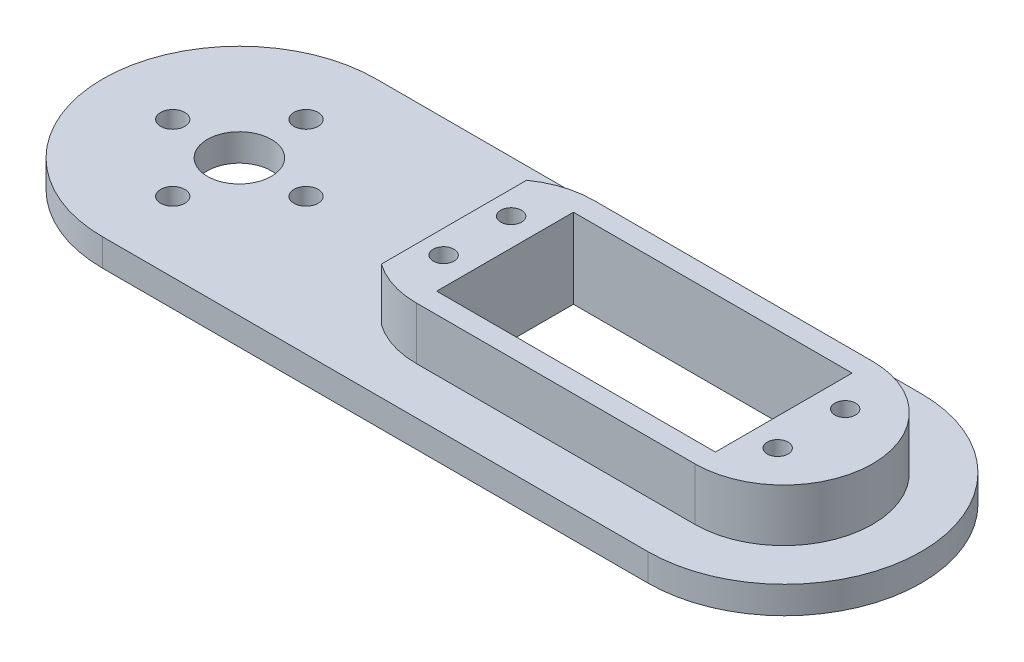
SolidWorks part; units mm, degrees
ref_plane "Front Plane" through (0, 0, 0) normal (0, 0, 1) x (1, 0, 0)
ref_plane "Top Plane" through (0, 0, 0) normal (0, 1, 0) x (1, 0, 0)
ref_plane "Right Plane" through (0, 0, 0) normal (1, 0, 0) x (0, 0, -1)
sketch "Sketch1" plane through (0, 0, 0) normal (0, 1, 0) x (1, 0, 0)
  line L0 (0, 15.5) -> (0, -15.5) construction
  line L1 (-15.5, 0) -> (15.5, 0) construction
  line L2 (-2.4674, 13.4022) -> (-4, 4) construction
  line L3 (4, -4) -> (-4, -4) construction
  line L4 (4, -4) -> (4, 4) construction
  line L5 (4, 4) -> (-4, 4) construction
  line L6 (-4, -4) -> (-4, 4) construction
  line L7 (4, -4) -> (-4, 4) construction
  line L8 (4, 4) -> (-4, -4) construction
  line L9 (-4, 4) -> (-2.4674, 13.4022)
  line L10 (4, 4) -> (2.4674, 13.4022)
  line L11 (4, -4) -> (2.4674, -13.4022)
  line L12 (-4, -4) -> (-2.4674, -13.4022)
  line L13 (-4, 4) -> (-12.5927, 2.4331) construction
  line L14 (-4, 4) -> (-12.4485, 2.4594)
  line L15 (-4, -4) -> (-12.4485, -2.4594)
  line L16 (4, -4) -> (12.4485, -2.4594)
  line L17 (4, 4) -> (12.4485, 2.4594)
  circle A0 centre (0, 0) radius 15.5 construction
  circle A1 centre (0, 0) radius 14.5 construction
  arc A2 (2.4674, 13.4022) -> (-2.4674, 13.4022) centre (0, 13) ccw
  arc A3 (2.4674, -13.4022) -> (-2.4674, -13.4022) centre (0, -13) cw
  arc A4 (-12.4485, 2.4594) -> (-12.4485, -2.4594) centre (-12, 0) ccw
  arc A5 (12.4485, 2.4594) -> (12.4485, -2.4594) centre (12, 0) cw
  circle A6 centre (0, 0) radius 12 construction
  circle A7 centre (0, 0) radius 9.5 construction
  circle A8 centre (0, 0) radius 7.5 construction
  circle A9 centre (0, 12) radius 0.5
  circle A10 centre (0, 9.5) radius 0.5
  circle A11 centre (0, 7.5) radius 0.5
  circle A12 centre (12, 0) radius 0.5
  circle A13 centre (9.5, 0) radius 0.5
  circle A14 centre (7.5, 0) radius 0.5
  circle A15 centre (0, -12) radius 0.5
  circle A16 centre (0, -9.5) radius 0.5
  circle A17 centre (0, -7.5) radius 0.5
  circle A18 centre (-12, 0) radius 0.5
  circle A19 centre (-9.5, 0) radius 0.5
  circle A20 centre (-7.5, 0) radius 0.5
  circle A21 centre (0, 0) radius 1.375
  point P59 (0, 0)
  dimension "D1" = 31
  dimension "D2" = 1
  dimension "D3" = 5
  dimension "D4" = 5
  dimension "D5" = 8
  dimension "D6" = 8
  dimension "D7" = 15
  dimension "D9" = 24
  dimension "D11" = 1
  dimension "D12" = 1
  dimension "D13" = 4
  dimension "D8" = 19
  dimension "D10" = 1
  dimension "D14" = 2.75
extrude "Boss-Extrude1" add sketch "Sketch1" along normal blind 2
sketch "Sketch4" plane through (0, 0, 0) normal (0, -1, 0) x (1, 0, 0)
  circle A0 centre (0, 0) radius 4.627
  circle A1 centre (0, 0) radius 2.627
  dimension "D1" = 9.254
  dimension "D2" = 2
extrude "Boss-Extrude3" add sketch "Sketch4" along normal blind 2.5
sketch "Sketch5" plane through (0, -2.5, 0) normal (0, -1, 0) x (1, 0, 0)
  line L0 (0, 0) -> (0, 0.6245) construction
  line L1 (0, 3.1016) -> (-0.2828, 2.6117)
  line L2 (0, 3.1016) -> (0.2828, 2.6117)
  line L3 (0.9584, 2.9498) -> (0.5381, 2.5713)
  line L4 (0.9584, 2.9498) -> (1.076, 2.3965)
  line L5 (1.8231, 2.5092) -> (1.3063, 2.2792)
  line L6 (1.8231, 2.5092) -> (1.7639, 1.9467)
  line L7 (2.5092, 1.8231) -> (1.9467, 1.7639)
  line L8 (2.5092, 1.8231) -> (2.2792, 1.3063)
  line L9 (2.9498, 0.9584) -> (2.3965, 1.076)
  line L10 (2.9498, 0.9584) -> (2.5713, 0.5381)
  line L11 (3.1016, 0) -> (2.6117, 0.2828)
  line L12 (3.1016, 0) -> (2.6117, -0.2828)
  line L13 (2.9498, -0.9584) -> (2.5713, -0.5381)
  line L14 (2.9498, -0.9584) -> (2.3965, -1.076)
  line L15 (2.5092, -1.8231) -> (2.2792, -1.3063)
  line L16 (2.5092, -1.8231) -> (1.9467, -1.7639)
  line L17 (1.8231, -2.5092) -> (1.7639, -1.9467)
  line L18 (1.8231, -2.5092) -> (1.3063, -2.2792)
  line L19 (0.9584, -2.9498) -> (1.076, -2.3965)
  line L20 (0.9584, -2.9498) -> (0.5381, -2.5713)
  line L21 (0, -3.1016) -> (0.2828, -2.6117)
  line L22 (0, -3.1016) -> (-0.2828, -2.6117)
  line L23 (-0.9584, -2.9498) -> (-0.5381, -2.5713)
  line L24 (-0.9584, -2.9498) -> (-1.076, -2.3965)
  line L25 (-1.8231, -2.5092) -> (-1.3063, -2.2792)
  line L26 (-1.8231, -2.5092) -> (-1.7639, -1.9467)
  line L27 (-2.5092, -1.8231) -> (-1.9467, -1.7639)
  line L28 (-2.5092, -1.8231) -> (-2.2792, -1.3063)
  line L29 (-2.9498, -0.9584) -> (-2.3965, -1.076)
  line L30 (-2.9498, -0.9584) -> (-2.5713, -0.5381)
  line L31 (-3.1016, 0) -> (-2.6117, -0.2828)
  line L32 (-3.1016, 0) -> (-2.6117, 0.2828)
  line L33 (-2.9498, 0.9584) -> (-2.5713, 0.5381)
  line L34 (-2.9498, 0.9584) -> (-2.3965, 1.076)
  line L35 (-2.5092, 1.8231) -> (-2.2792, 1.3063)
  line L36 (-2.5092, 1.8231) -> (-1.9467, 1.7639)
  line L37 (-1.8231, 2.5092) -> (-1.7639, 1.9467)
  line L38 (-1.8231, 2.5092) -> (-1.3063, 2.2792)
  line L39 (-0.9584, 2.9498) -> (-1.076, 2.3965)
  line L40 (-0.9584, 2.9498) -> (-0.5381, 2.5713)
  circle A0 centre (0, 0) radius 2.627 construction
  arc A1 (-2.2792, 1.3063) -> (-2.3965, 1.076) centre (0, 0) ccw
  arc A2 (-1.7639, 1.9467) -> (-1.9467, 1.7639) centre (0, 0) ccw
  arc A3 (-1.076, 2.3965) -> (-1.3063, 2.2792) centre (0, 0) ccw
  arc A4 (-0.2828, 2.6117) -> (-0.5381, 2.5713) centre (0, 0) ccw
  arc A5 (0.5381, 2.5713) -> (0.2828, 2.6117) centre (0, 0) ccw
  arc A6 (1.3063, 2.2792) -> (1.076, 2.3965) centre (0, 0) ccw
  arc A7 (1.9467, 1.7639) -> (1.7639, 1.9467) centre (0, 0) ccw
  arc A8 (2.3965, 1.076) -> (2.2792, 1.3063) centre (0, 0) ccw
  arc A9 (2.6117, 0.2828) -> (2.5713, 0.5381) centre (0, 0) ccw
  arc A10 (2.5713, -0.5381) -> (2.6117, -0.2828) centre (0, 0) ccw
  arc A11 (2.2792, -1.3063) -> (2.3965, -1.076) centre (0, 0) ccw
  arc A12 (1.7639, -1.9467) -> (1.9467, -1.7639) centre (0, 0) ccw
  arc A13 (1.076, -2.3965) -> (1.3063, -2.2792) centre (0, 0) ccw
  arc A14 (0.2828, -2.6117) -> (0.5381, -2.5713) centre (0, 0) ccw
  arc A15 (-0.5381, -2.5713) -> (0, -2.627) centre (0, 0) ccw
  arc A16 (-1.3063, -2.2792) -> (-1.076, -2.3965) centre (0, 0) ccw
  arc A17 (-1.9467, -1.7639) -> (-1.7639, -1.9467) centre (0, 0) ccw
  arc A18 (-2.3965, -1.076) -> (-2.2792, -1.3063) centre (0, 0) ccw
  arc A19 (-2.6117, -0.2828) -> (-2.5713, -0.5381) centre (0, 0) ccw
  arc A20 (-2.5713, 0.5381) -> (-2.6117, 0.2828) centre (0, 0) ccw
  point P68 (0, 0)
  circle M5 centre (0, 0) radius 2.627
  dimension "D1" = 30
  dimension "D2" = 3.1016
  dimension "D3" = 20
extrude "Cut-Extrude3" cut sketch "Sketch5" against normal up to surface (2.5 mm away) contours L36 L35 M5 | L34 L33 M5 | L32 L31 M5 | L30 L29 M5 | L28 L27 M5 | L26 L25 M5 | L24 L23 M5 | L0 L21 M5 | L22 L0 M5 | L20 L19 M5 | L18 L17 M5 | L16 L15 M5 | L14 L13 M5 | L12 L11 M5 | L10 L9 M5 | L8 L7 M5 | L6 L5 M5 | L4 L3 M5 | L0 L2 M5 | L0 L1 M5 | L40 L39 M5 | L38 L37 M5 region at (0, -2.5, 2.7818) region at (-0.8596, -2.5, 2.6457) region at (0.8596, -2.5, 2.6457) region at (-1.6351, -2.5, 2.2506) region at (1.6351, -2.5, 2.2506) region at (-2.2506, -2.5, 1.6351) region at (2.2506, -2.5, 1.6351) region at (-2.6457, -2.5, 0.8596) region at (2.6457, -2.5, 0.8596) region at (-2.7818, -2.5, 0) region at (2.7818, -2.5, 0) region at (-2.6457, -2.5, -0.8596) region at (2.6457, -2.5, -0.8596) region at (-2.2506, -2.5, -1.6351) region at (2.2506, -2.5, -1.6351) region at (-1.6351, -2.5, -2.2506) region at (1.6351, -2.5, -2.2506) region at (-0.8596, -2.5, -2.6457) region at (0.8596, -2.5, -2.6457) region at (0, -2.5, -2.7818) up to face at (0, 0, 1.375)
sketch "Sketch6" plane through (0, 2, 0) normal (0, 1, 0) x (1, 0, 0)
  circle A0 centre (0, 0) radius 20.066
  circle A2 centre (0, 0) radius 3.75
  dimension "D1" = 40.132
extrude "Boss-Extrude6" add sketch "Sketch6" against normal blind 2.54
sketch "Sketch7" plane through (0, 2, 0) normal (0, 1, 0) x (1, 0, 0)
  circle A0 centre (0, 9.779) radius 1.778
extrude "Cut-Extrude4" cut sketch "Sketch7" against normal blind 2.54
pattern_circular "CirPattern1" count 4 over 360 about axis through (0, 2, 0) along (0, -1, 0) of "Cut-Extrude4"
sketch "Esquisse1" plane through (0, 2, 0) normal (0, 1, 0) x (1, 0, 0)
  line L0 (0, 20.066) -> (80.01, 20.066)
  line L1 (0, -20.066) -> (80.01, -20.066)
  circle A0 centre (0, 0) radius 20.066 construction
  arc A1 (80.01, 20.066) -> (80.01, -20.066) centre (80.01, 0) cw
  arc A2 (0, -20.066) -> (0, 20.066) centre (0, 0) ccw
  dimension "D1" = 80.01
  dimension "D2" = 80.01
extrude "Boss.-Extru.1" add sketch "Esquisse1" along normal blind 2.2225 and the other way blind 2.54 contours L1 A1 L0 A2
sketch "Esquisse3" plane through (0, 2, 0) normal (0, 1, 0) x (1, 0, 0)
  circle A0 centre (0, 0) radius 20.066
  circle A1 centre (9.779, 0) radius 1.778
  circle A2 centre (0, 9.779) radius 1.778
  circle A3 centre (-9.779, 0) radius 1.778
  circle A4 centre (0, -9.779) radius 1.778
  circle A5 centre (0, 0) radius 1.375
extrude "Boss.-Extru.2" add sketch "Esquisse3" along normal blind 2.2225
sketch "Esquisse4" plane through (0, -0.54, 0) normal (0, -1, 0) x (1, 0, 0)
  line L0 (0, 20.066) -> (80.01, 20.066) construction
  line L1 (80.01, 10.16) -> (39.116, 10.16)
  line L2 (39.116, 10.16) -> (39.116, -9.906)
  line L3 (39.116, -9.906) -> (80.01, -9.906)
  line L4 (80.01, -9.906) -> (80.01, 10.16)
  dimension "D1" = 9.906
  dimension "D2" = 20.066
  dimension "D3" = 40.894
extrude "Enlèv. mat.-Extru.1" cut sketch "Esquisse4" against normal up to next
sketch "Esquisse5" plane through (0, -0.54, 0) normal (0, -1, 0) x (-1, 0, 0)
  line L0 (-39.116, -10.16) -> (-39.116, 9.906) construction
  line L1 (-39.116, 9.906) -> (-80.01, 9.906) construction
  line L2 (-80.01, -10.16) -> (-39.116, -10.16) construction
  line L3 (-80.01, 9.906) -> (-80.01, -10.16) construction
  circle A0 centre (-35.052, -5.08) radius 1.524
  circle A1 centre (-35.052, 4.826) radius 1.524
  circle A2 centre (-84.074, -5.08) radius 1.524
  circle A3 centre (-84.074, 4.826) radius 1.524
  dimension "D2" = 4.064
  dimension "D3" = 5.08
  dimension "D4" = 5.08
  dimension "D5" = 5.08
  dimension "D6" = 5.08
  dimension "D7" = 4.064
  dimension "D8" = 4.064
  dimension "D9" = 3.048
  dimension "D10" = 3.048
  dimension "D11" = 3.048
  dimension "D12" = 3.048
  dimension "D1" = 4.064
extrude "Enlèv. mat.-Extru.2" cut sketch "Esquisse5" against normal through all
sketch "Esquisse6" plane through (0, 4.2225, 0) normal (0, 1, 0) x (1, 0, 0)
  line L1 (-24.0414, -40.1247) -> (105.7665, -40.1247)
  line L2 (-24.0414, -40.1247) -> (-24.0414, 44.3818)
  line L3 (-24.0414, 44.3818) -> (105.7665, 44.3818)
  line L4 (105.7665, -40.1247) -> (105.7665, 44.3818)
extrude "Enlèv. mat.-Extru.3" cut sketch "Esquisse6" against normal blind 0.76
sketch "Esquisse7" plane through (0, -2.5, 0) normal (0, -1, 0) x (-1, 0, 0)
  circle A0 centre (0, 0) radius 4.7
  dimension "D1" = 9.4
extrude "Enlèv. mat.-Extru.4" cut sketch "Esquisse7" against normal through all
sketch "Esquisse8" plane through (0, 3.4625, 0) normal (0, 1, 0) x (1, 0, 0)
  line L0 (80.01, -13.16) -> (39.116, -13.16)
  line L1 (80.01, 12.906) -> (39.116, 12.906)
  line L3 (39.116, -10.16) -> (80.01, -10.16)
  line L4 (39.116, -10.16) -> (39.116, 9.906)
  line L5 (39.116, 9.906) -> (80.01, 9.906)
  line L6 (80.01, -10.16) -> (80.01, 9.906)
  arc A0 (80.01, -13.16) -> (80.01, 12.906) centre (80.01, -0.127) ccw
  arc A1 (39.116, -13.16) -> (39.116, 12.906) centre (39.116, -0.127) cw
  circle A2 centre (84.074, -5.08) radius 1.524
  circle A3 centre (84.074, 4.826) radius 1.524
  circle A4 centre (35.052, -5.08) radius 1.524
  circle A5 centre (35.052, 4.826) radius 1.524
  dimension "D3" = 13.033
  dimension "D1" = 3
  dimension "D2" = 3
extrude "Boss.-Extru.3" add sketch "Esquisse8" along normal blind 7.7
sketch "Esquisse9" plane through (0, 11.1625, 0) normal (0, 1, 0) x (1, 0, 0)
  line L0 (31.616, 12.906) -> (24.1634, 12.906)
  line L1 (31.616, -13.16) -> (31.616, 12.906)
  line L2 (24.1634, 12.906) -> (24.1634, -13.16)
  line L3 (24.1634, -13.16) -> (31.616, -13.16)
extrude "Enlèv. mat.-Extru.5" cut sketch "Esquisse9" against normal blind 7.7
